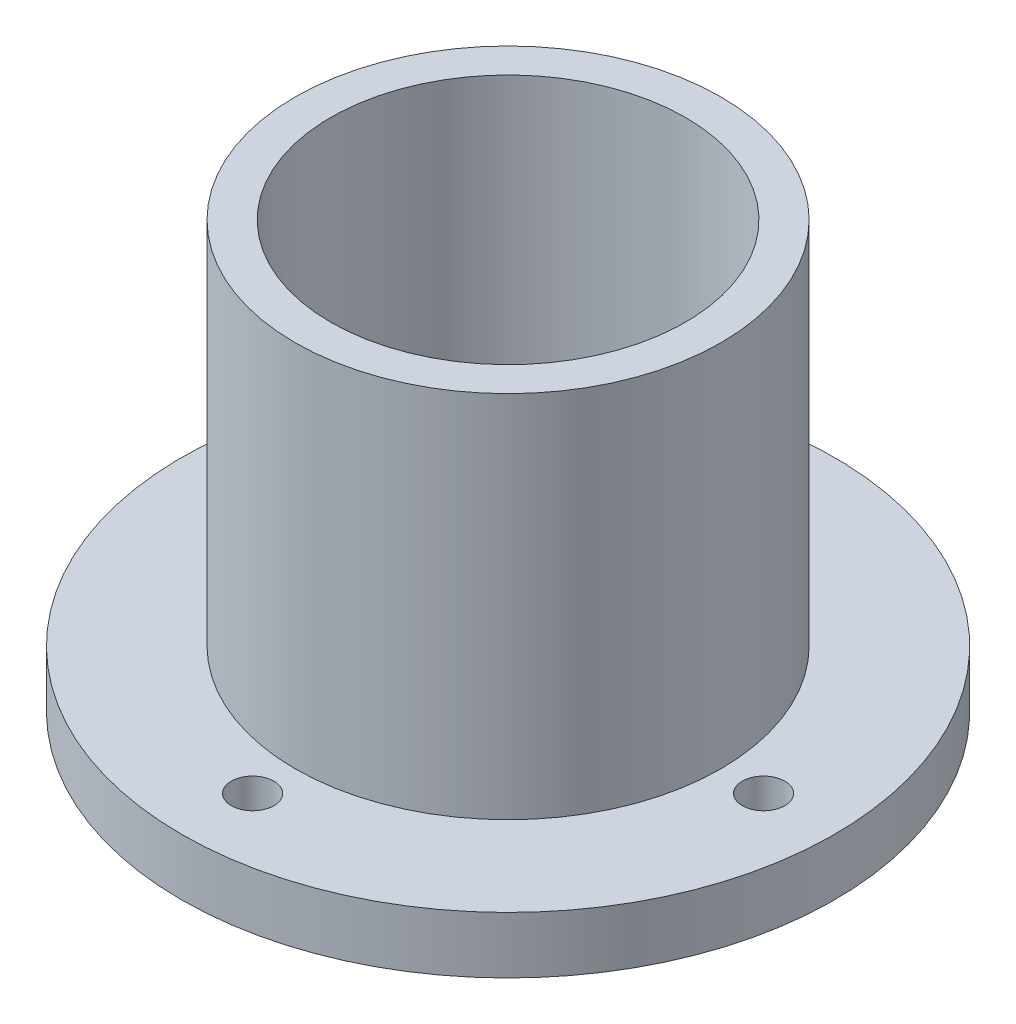
SolidWorks part; units mm, degrees
ref_plane "前视基准面" through (0, 0, 0) normal (0, 0, 1) x (1, 0, 0)
ref_plane "上视基准面" through (0, 0, 0) normal (0, 1, 0) x (1, 0, 0)
ref_plane "右视基准面" through (0, 0, 0) normal (1, 0, 0) x (0, 0, -1)
sketch "草图1" plane through (0, 0, 0) normal (0, 1, 0) x (1, 0, 0)
  circle A0 centre (0, 0) radius 12.5
  circle A1 centre (0, 0) radius 15
  circle A2 centre (0, 0) radius 23
  dimension "D1" = 25
  dimension "D2" = 30
  dimension "D3" = 46
extrude "凸台-拉伸1" add sketch "草图1" along normal blind 30 contours A1 A0 region at (-14.5757, 0, 0)
extrude "凸台-拉伸2" add sketch "草图1<3>" along normal blind 4 contours A2 A1 region at (-22.3495, 0, 0)
sketch "草图1<3>" plane through (0, 0, 0) normal (0, 1, 0) x (1, 0, 0) same geometry as "草图1"
sketch "草图3" plane through (0, 0, 0) normal (0, -1, 0) x (1, 0, 0)
  circle A0 centre (0, 18) radius 1.5
  circle A1 centre (18, 0) radius 1.5
  circle A2 centre (0, -18) radius 1.5
  circle A3 centre (-18, 0) radius 1.5
  circle A4 centre (0, 0) radius 12.5 construction
  point P12 (0, 0)
  dimension "D1" = 18
  dimension "D2" = 3
  dimension "D4" = 18
  dimension "D5" = 18
  dimension "D6" = 18
  dimension "D3" = 4
extrude "切除-拉伸3" cut sketch "草图3" against normal up to next
